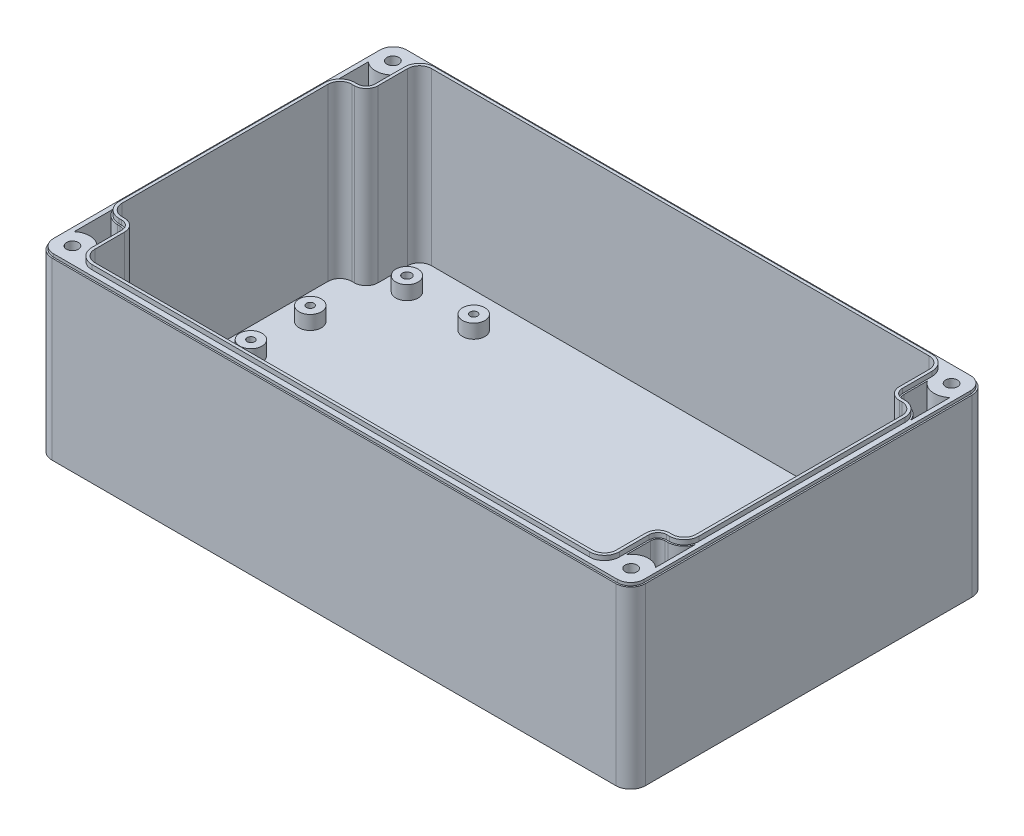
SolidWorks part; units mm, degrees
ref_plane "Front Plane" through (0, 0, 0) normal (0, 0, 1) x (1, 0, 0)
ref_plane "Top Plane" through (0, 0, 0) normal (0, 1, 0) x (1, 0, 0)
ref_plane "Right Plane" through (0, 0, 0) normal (1, 0, 0) x (0, 0, -1)
sketch "Sketch1" plane through (0, 0, 0) normal (0, 1, 0) x (1, 0, 0)
  line L1 (-100, 60) -> (100, 60)
  line L2 (-100, 60) -> (-100, -60)
  line L3 (-100, -60) -> (100, -60)
  line L4 (100, 60) -> (100, -60)
  line L5 (-100, 60) -> (100, -60) construction
  line L6 (-100, -60) -> (100, 60) construction
  point P0 (0, 0)
  dimension "D1" = 200
  dimension "D2" = 120
extrude "Boss-Extrude1" add sketch "Sketch1" along normal blind 60
fillet "Fillet1" radius 5 4 edges at (-100, 30, -60) (100, 30, -60) (100, 30, 60) (-100, 30, 60)
sketch "Sketch2" plane through (0, 60, 0) normal (0, 1, 0) x (1, 0, 0)
  line L0 (0, 60) -> (0, -60) construction
  line L1 (96.7, 56.7) -> (-96.7, 56.7)
  line L2 (96.7, 56.7) -> (96.7, -56.7)
  line L3 (96.7, -56.7) -> (-96.7, -56.7)
  line L4 (-96.7, 56.7) -> (-96.7, -56.7)
  line L5 (96.7, 56.7) -> (-96.7, -56.7) construction
  line L6 (96.7, -56.7) -> (-96.7, 56.7) construction
  line L7 (95, 60) -> (-95, 60) construction
  line L8 (-95, -60) -> (95, -60) construction
  line L9 (-100, 0) -> (99.9439, 0) construction
  line L10 (-100, 55) -> (-100, -55) construction
  line L12 (87.85, -56.7) -> (-87.85, -56.7)
  line L13 (87.85, -56.7) -> (87.85, 56.7)
  line L14 (87.85, 56.7) -> (-87.85, 56.7)
  line L15 (-87.85, -56.7) -> (-87.85, 56.7)
  line L16 (87.85, -56.7) -> (-87.85, 56.7) construction
  line L17 (87.85, 56.7) -> (-87.85, -56.7) construction
  line L18 (96.7, -38.7) -> (-96.7, -38.7)
  line L19 (96.7, -38.7) -> (96.7, 38.7)
  line L20 (96.7, 38.7) -> (-96.7, 38.7)
  line L21 (-96.7, -38.7) -> (-96.7, 38.7)
  line L22 (96.7, -38.7) -> (-96.7, 38.7) construction
  line L23 (96.7, 38.7) -> (-96.7, -38.7) construction
  circle A0 centre (-94.15, 54) radius 2
  circle A2 centre (94.15, 54) radius 2
  circle A3 centre (94.15, -54) radius 2
  circle A4 centre (-94.15, -54) radius 2
  point P0 (0, 0)
  point P18 (0, 0)
  point P19 (0, 0)
  dimension "D5" = 4
  dimension "D1" = 193.4
  dimension "D2" = 113.4
  dimension "D3" = 188.3
  dimension "D4" = 108
  dimension "D6" = 175.7
  dimension "D7" = 77.4
extrude "Cut-Extrude1" cut sketch "Sketch2" against normal offset from surface (56 mm away) 4 contours L20 L13 L1 L15 | L13 L20 L15 L18 | L13 L18 L15 L3 | L15 L20 L4 L18 | L2 L20 L13 L18 | A0 | A4 | A2 | A3 region at (0, 60, -47.7) region at (92.275, 60, 0) region at (0, 60, 0) region at (-92.275, 60, 0) region at (0, 60, 47.7) up to face at (0, 0, 0)
fillet "Fillet2" radius 4 12 edges at (87.85, 32, -56.7) (87.85, 32, -38.7) (96.7, 32, -38.7) (96.7, 32, 38.7) (87.85, 32, 38.7) (87.85, 32, 56.7) (-87.85, 32, 56.7) (-87.85, 32, 38.7) (-96.7, 32, 38.7) (-96.7, 32, -38.7) (-87.85, 32, -56.7) (-87.85, 32, -38.7)
sketch "Sketch3" plane through (0, 60, 0) normal (0, 1, 0) x (1, 0, 0)
  line L1 (83.85, 57.7) -> (-83.85, 57.7)
  line L2 (-88.85, 52.7) -> (-88.85, 42.7)
  line L3 (-91.85, 39.7) -> (-92.7, 39.7)
  line L4 (-97.7, 34.7) -> (-97.7, -34.7)
  line L5 (-92.7, -39.7) -> (-91.85, -39.7)
  line L6 (-88.85, -42.7) -> (-88.85, -52.7)
  line L7 (-83.85, -57.7) -> (83.85, -57.7)
  line L8 (88.85, -52.7) -> (88.85, -42.7)
  line L9 (91.85, -39.7) -> (92.7, -39.7)
  line L10 (97.7, -34.7) -> (97.7, 34.7)
  line L11 (92.7, 39.7) -> (91.85, 39.7)
  line L12 (88.85, 42.7) -> (88.85, 52.7)
  line L13 (87.85, 42.7) -> (87.85, 52.7)
  line L14 (92.7, 38.7) -> (91.85, 38.7)
  line L15 (96.7, -34.7) -> (96.7, 34.7)
  line L16 (91.85, -38.7) -> (92.7, -38.7)
  line L17 (87.85, -52.7) -> (87.85, -42.7)
  line L18 (-83.85, -56.7) -> (83.85, -56.7)
  line L19 (-87.85, -42.7) -> (-87.85, -52.7)
  line L20 (-92.7, -38.7) -> (-91.85, -38.7)
  line L21 (-96.7, 34.7) -> (-96.7, -34.7)
  line L22 (-91.85, 38.7) -> (-92.7, 38.7)
  line L23 (-87.85, 52.7) -> (-87.85, 42.7)
  line L24 (83.85, 56.7) -> (-83.85, 56.7)
  line L25 (87.85, 42.7) -> (87.85, 52.7)
  line L26 (92.7, 38.7) -> (91.85, 38.7)
  line L27 (96.7, -34.7) -> (96.7, 34.7)
  line L28 (91.85, -38.7) -> (92.7, -38.7)
  line L29 (87.85, -52.7) -> (87.85, -42.7)
  line L30 (-83.85, -56.7) -> (83.85, -56.7)
  line L31 (-87.85, -42.7) -> (-87.85, -52.7)
  line L32 (-92.7, -38.7) -> (-91.85, -38.7)
  line L33 (-96.7, 34.7) -> (-96.7, -34.7)
  line L34 (-91.85, 38.7) -> (-92.7, 38.7)
  line L35 (-87.85, 52.7) -> (-87.85, 42.7)
  line L36 (83.85, 56.7) -> (-83.85, 56.7)
  arc A0 (-83.85, 57.7) -> (-88.85, 52.7) centre (-83.85, 52.7) ccw
  arc A1 (-91.85, 39.7) -> (-88.85, 42.7) centre (-91.85, 42.7) ccw
  arc A2 (-92.7, 39.7) -> (-97.7, 34.7) centre (-92.7, 34.7) ccw
  arc A3 (-97.7, -34.7) -> (-92.7, -39.7) centre (-92.7, -34.7) ccw
  arc A4 (-88.85, -42.7) -> (-91.85, -39.7) centre (-91.85, -42.7) ccw
  arc A5 (-88.85, -52.7) -> (-83.85, -57.7) centre (-83.85, -52.7) ccw
  arc A6 (83.85, -57.7) -> (88.85, -52.7) centre (83.85, -52.7) ccw
  arc A7 (91.85, -39.7) -> (88.85, -42.7) centre (91.85, -42.7) ccw
  arc A8 (92.7, -39.7) -> (97.7, -34.7) centre (92.7, -34.7) ccw
  arc A9 (97.7, 34.7) -> (92.7, 39.7) centre (92.7, 34.7) ccw
  arc A10 (88.85, 42.7) -> (91.85, 39.7) centre (91.85, 42.7) ccw
  arc A11 (88.85, 52.7) -> (83.85, 57.7) centre (83.85, 52.7) ccw
  arc A12 (87.85, 42.7) -> (91.85, 38.7) centre (91.85, 42.7) ccw
  arc A13 (96.7, 34.7) -> (92.7, 38.7) centre (92.7, 34.7) ccw
  arc A14 (92.7, -38.7) -> (96.7, -34.7) centre (92.7, -34.7) ccw
  arc A15 (91.85, -38.7) -> (87.85, -42.7) centre (91.85, -42.7) ccw
  arc A16 (83.85, -56.7) -> (87.85, -52.7) centre (83.85, -52.7) ccw
  arc A17 (-87.85, -52.7) -> (-83.85, -56.7) centre (-83.85, -52.7) ccw
  arc A18 (-87.85, -42.7) -> (-91.85, -38.7) centre (-91.85, -42.7) ccw
  arc A19 (-96.7, -34.7) -> (-92.7, -38.7) centre (-92.7, -34.7) ccw
  arc A20 (-92.7, 38.7) -> (-96.7, 34.7) centre (-92.7, 34.7) ccw
  arc A21 (-91.85, 38.7) -> (-87.85, 42.7) centre (-91.85, 42.7) ccw
  arc A22 (-83.85, 56.7) -> (-87.85, 52.7) centre (-83.85, 52.7) ccw
  arc A23 (87.85, 52.7) -> (83.85, 56.7) centre (83.85, 52.7) ccw
  arc A24 (87.85, 42.7) -> (91.85, 38.7) centre (91.85, 42.7) ccw
  arc A25 (96.7, 34.7) -> (92.7, 38.7) centre (92.7, 34.7) ccw
  arc A26 (92.7, -38.7) -> (96.7, -34.7) centre (92.7, -34.7) ccw
  arc A27 (91.85, -38.7) -> (87.85, -42.7) centre (91.85, -42.7) ccw
  arc A28 (83.85, -56.7) -> (87.85, -52.7) centre (83.85, -52.7) ccw
  arc A29 (-87.85, -52.7) -> (-83.85, -56.7) centre (-83.85, -52.7) ccw
  arc A30 (-87.85, -42.7) -> (-91.85, -38.7) centre (-91.85, -42.7) ccw
  arc A31 (-96.7, -34.7) -> (-92.7, -38.7) centre (-92.7, -34.7) ccw
  arc A32 (-92.7, 38.7) -> (-96.7, 34.7) centre (-92.7, 34.7) ccw
  arc A33 (-91.85, 38.7) -> (-87.85, 42.7) centre (-91.85, 42.7) ccw
  arc A34 (-83.85, 56.7) -> (-87.85, 52.7) centre (-83.85, 52.7) ccw
  arc A35 (87.85, 52.7) -> (83.85, 56.7) centre (83.85, 52.7) ccw
  dimension "D1" = 0
  dimension "D2" = 1
extrude "Boss-Extrude2" add sketch "Sketch3" along normal blind 1.55
sketch "Sketch4" plane through (0, 4, 0) normal (0, 1, 0) x (1, 0, 0)
  circle A1 centre (-94.15, 54) radius 2
  circle A2 centre (-94.15, 54) radius 2
  circle A3 centre (94.15, 54) radius 2
  circle A4 centre (94.15, 54) radius 2
  circle A5 centre (-94.15, -54) radius 2
  circle A6 centre (-94.15, -54) radius 2
  circle A7 centre (94.15, -54) radius 2
  circle A8 centre (94.15, -54) radius 2
  dimension "D1" = 0
  dimension "D2" = 0
  dimension "D3" = 0
  dimension "D4" = 0
extrude "Cut-Extrude2" cut sketch "Sketch4" against normal up to next
sketch "Sketch5" plane through (0, 0, 0) normal (0, -1, 0) x (1, 0, 0)
  circle A0 centre (-94.15, 54) radius 3.45
  circle A1 centre (94.15, 54) radius 3.45
  circle A2 centre (94.15, -54) radius 3.45
  circle A3 centre (-94.15, -54) radius 3.45
  dimension "D1" = 6.9
extrude "Cut-Extrude3" cut sketch "Sketch5" against normal blind 52
sketch "Sketch6" plane through (0, 60, 0) normal (0, 1, 0) x (1, 0, 0)
  line L8 (95, 58) -> (-95, 58)
  line L9 (-98, 55) -> (-98, -55)
  line L10 (-95, -58) -> (95, -58)
  line L11 (98, -55) -> (98, 55)
  line L12 (95, 58) -> (-95, 58)
  line L13 (-98, 55) -> (-98, -55)
  line L14 (-95, -58) -> (95, -58)
  line L15 (98, -55) -> (98, 55)
  line L25 (-100, 55) -> (-100, -55) construction
  line L37 (83.85, 58.2) -> (-83.85, 58.2)
  line L38 (89.35, 42.7) -> (89.35, 52.7)
  line L39 (92.7, 40.2) -> (91.85, 40.2)
  line L40 (98.2, -34.7) -> (98.2, 34.7)
  line L41 (91.85, -40.2) -> (92.7, -40.2)
  line L42 (89.35, -52.7) -> (89.35, -42.7)
  line L43 (-83.85, -58.2) -> (83.85, -58.2)
  line L44 (-89.35, -42.7) -> (-89.35, -52.7)
  line L45 (-92.7, -40.2) -> (-91.85, -40.2)
  line L46 (-98.2, 34.7) -> (-98.2, -34.7)
  line L47 (-91.85, 40.2) -> (-92.7, 40.2)
  line L48 (-89.35, 52.7) -> (-89.35, 42.7)
  line L49 (83.85, 58.2) -> (-83.85, 58.2)
  line L50 (89.35, 42.7) -> (89.35, 52.7)
  line L51 (92.7, 40.2) -> (91.85, 40.2)
  line L52 (98.2, -34.7) -> (98.2, 34.7)
  line L53 (91.85, -40.2) -> (92.7, -40.2)
  line L54 (89.35, -52.7) -> (89.35, -42.7)
  line L55 (-83.85, -58.2) -> (83.85, -58.2)
  line L56 (-89.35, -42.7) -> (-89.35, -52.7)
  line L57 (-92.7, -40.2) -> (-91.85, -40.2)
  line L58 (-98.2, 34.7) -> (-98.2, -34.7)
  line L59 (-91.85, 40.2) -> (-92.7, 40.2)
  line L60 (-89.35, 52.7) -> (-89.35, 42.7)
  arc A8 (-95, 58) -> (-98, 55) centre (-95, 55) ccw
  arc A9 (-98, -55) -> (-95, -58) centre (-95, -55) ccw
  arc A10 (95, -58) -> (98, -55) centre (95, -55) ccw
  arc A11 (98, 55) -> (95, 58) centre (95, 55) ccw
  arc A12 (-95, 58) -> (-98, 55) centre (-95, 55) ccw
  arc A13 (-98, -55) -> (-95, -58) centre (-95, -55) ccw
  arc A14 (95, -58) -> (98, -55) centre (95, -55) ccw
  arc A15 (98, 55) -> (95, 58) centre (95, 55) ccw
  circle A24 centre (-94.15, 54) radius 5.85
  circle A25 centre (94.15, 54) radius 5.85
  circle A26 centre (94.15, -54) radius 5.85
  circle A27 centre (-94.15, -54) radius 5.85
  arc A36 (89.35, 52.7) -> (83.85, 58.2) centre (83.85, 52.7) ccw
  arc A37 (89.35, 42.7) -> (91.85, 40.2) centre (91.85, 42.7) ccw
  arc A38 (98.2, 34.7) -> (92.7, 40.2) centre (92.7, 34.7) ccw
  arc A39 (92.7, -40.2) -> (98.2, -34.7) centre (92.7, -34.7) ccw
  arc A40 (91.85, -40.2) -> (89.35, -42.7) centre (91.85, -42.7) ccw
  arc A41 (83.85, -58.2) -> (89.35, -52.7) centre (83.85, -52.7) ccw
  arc A42 (-89.35, -52.7) -> (-83.85, -58.2) centre (-83.85, -52.7) ccw
  arc A43 (-89.35, -42.7) -> (-91.85, -40.2) centre (-91.85, -42.7) ccw
  arc A44 (-98.2, -34.7) -> (-92.7, -40.2) centre (-92.7, -34.7) ccw
  arc A45 (-92.7, 40.2) -> (-98.2, 34.7) centre (-92.7, 34.7) ccw
  arc A46 (-91.85, 40.2) -> (-89.35, 42.7) centre (-91.85, 42.7) ccw
  arc A47 (-83.85, 58.2) -> (-89.35, 52.7) centre (-83.85, 52.7) ccw
  arc A48 (89.35, 52.7) -> (83.85, 58.2) centre (83.85, 52.7) ccw
  arc A49 (89.35, 42.7) -> (91.85, 40.2) centre (91.85, 42.7) ccw
  arc A50 (98.2, 34.7) -> (92.7, 40.2) centre (92.7, 34.7) ccw
  arc A51 (92.7, -40.2) -> (98.2, -34.7) centre (92.7, -34.7) ccw
  arc A52 (91.85, -40.2) -> (89.35, -42.7) centre (91.85, -42.7) ccw
  arc A53 (83.85, -58.2) -> (89.35, -52.7) centre (83.85, -52.7) ccw
  arc A54 (-89.35, -52.7) -> (-83.85, -58.2) centre (-83.85, -52.7) ccw
  arc A55 (-89.35, -42.7) -> (-91.85, -40.2) centre (-91.85, -42.7) ccw
  arc A56 (-98.2, -34.7) -> (-92.7, -40.2) centre (-92.7, -34.7) ccw
  arc A57 (-92.7, 40.2) -> (-98.2, 34.7) centre (-92.7, 34.7) ccw
  arc A58 (-91.85, 40.2) -> (-89.35, 42.7) centre (-91.85, 42.7) ccw
  arc A59 (-83.85, 58.2) -> (-89.35, 52.7) centre (-83.85, 52.7) ccw
  dimension "D1" = 2
  dimension "D2" = 0.5
extrude "Cut-Extrude4" cut sketch "Sketch6" against normal up to surface (56 mm away) contours L59 A58 L60 A24 L13 A57 | A50 L15 A25 L50 A49 L51 | L53 A52 L54 A26 L15 A51 | A56 L13 A27 L56 A55 L57 region at (93.8916, 60, -44.1874) region at (93.8916, 60, 44.1874) region at (-93.8916, 60, -44.1874) region at (-93.8916, 60, 44.1874) up to face at (0, 4, 0)
sketch "Sketch7" plane through (0, 0, 0) normal (0, -1, 0) x (1, 0, 0)
  line L0 (-94.15, 54) -> (-94.15, -54) construction
  line L1 (94.15, -45) -> (-94.15, -45)
  line L2 (94.15, -45) -> (94.15, 45)
  line L3 (94.15, 45) -> (-94.15, 45)
  line L4 (-94.15, -45) -> (-94.15, 45)
  line L5 (94.15, -45) -> (-94.15, 45) construction
  line L6 (94.15, 45) -> (-94.15, -45) construction
  circle A0 centre (-94.15, 45) radius 2.225
  circle A1 centre (94.15, 45) radius 2.225
  circle A2 centre (94.15, -45) radius 2.225
  circle A3 centre (-94.15, -45) radius 2.225
  point P0 (0, 0)
  dimension "D2" = 4.45
  dimension "D1" = 90
extrude "Cut-Extrude5" cut sketch "Sketch7" against normal up to next contours A0 | A1 | A2 | A3
sketch "Sketch8" plane through (0, 4, 0) normal (0, 1, 0) x (1, 0, 0)
  line L0 (0, 60) -> (0, -60) construction
  line L1 (95, 60) -> (-95, 60) construction
  line L2 (-95, -60) -> (95, -60) construction
  line L3 (-100, 0) -> (100, 0) construction
  line L4 (-100, 55) -> (-100, -55) construction
  line L5 (100, -55) -> (100, 55) construction
  line L6 (-80.4, 45) -> (80.4, 45) construction
  line L7 (-80.4, 45) -> (-80.4, -45) construction
  line L8 (-88, 60) -> (-88, -60) construction
  circle A0 centre (-80.4, 45) radius 3.75
  circle A1 centre (-80.4, 45) radius 1.5
  circle A2 centre (80.4, 45) radius 3.75
  circle A3 centre (80.4, 45) radius 1.5
  circle A4 centre (80.4, -45) radius 3.75
  circle A5 centre (80.4, -45) radius 1.5
  circle A6 centre (-80.4, -45) radius 3.75
  circle A7 centre (-80.4, -45) radius 1.5
  circle A8 centre (-57.9, 45) radius 3.75
  circle A9 centre (-57.9, 45) radius 1.25
  circle A12 centre (-57.9, -45) radius 1.25
  circle A13 centre (-57.9, -45) radius 3.75
  circle A16 centre (-88, 0) radius 3.75
  circle A17 centre (-88, 0) radius 1.25
  circle A18 centre (-88, 20) radius 3.75
  circle A19 centre (-88, 20) radius 1.25
  circle A20 centre (-88, -20) radius 1.25
  circle A21 centre (-88, -20) radius 3.75
  circle A22 centre (88, -20) radius 3.75
  circle A23 centre (88, -20) radius 1.25
  circle A24 centre (88, 0) radius 1.25
  circle A25 centre (88, 0) radius 3.75
  circle A26 centre (88, 20) radius 3.75
  circle A27 centre (88, 20) radius 1.25
  dimension "D1" = 7.5
  dimension "D2" = 3
  dimension "D5" = 2.5
  dimension "D3" = 160.8
  dimension "D4" = 90
  dimension "D6" = 22.5
  dimension "D7" = 176
  dimension "D8" = 40
extrude "Boss-Extrude3" add sketch "Sketch8" along normal blind 4.7
sketch "Sketch9" plane through (0, 60, 0) normal (0, 1, 0) x (1, 0, 0)
  line L0 (95, 59.5) -> (-95, 59.5)
  line L1 (-99.5, 55) -> (-99.5, -55)
  line L2 (-95, -59.5) -> (95, -59.5)
  line L3 (99.5, -55) -> (99.5, 55)
  line L4 (95, 60) -> (-95, 60)
  line L5 (-100, 55) -> (-100, -55)
  line L6 (-95, -60) -> (95, -60)
  line L7 (100, -55) -> (100, 55)
  line L8 (95, 60) -> (-95, 60)
  line L9 (-100, 55) -> (-100, -55)
  line L10 (-95, -60) -> (95, -60)
  line L11 (100, -55) -> (100, 55)
  arc A0 (-95, 59.5) -> (-99.5, 55) centre (-95, 55) ccw
  arc A1 (-99.5, -55) -> (-95, -59.5) centre (-95, -55) ccw
  arc A2 (95, -59.5) -> (99.5, -55) centre (95, -55) ccw
  arc A3 (99.5, 55) -> (95, 59.5) centre (95, 55) ccw
  arc A4 (-95, 60) -> (-100, 55) centre (-95, 55) ccw
  arc A5 (-100, -55) -> (-95, -60) centre (-95, -55) ccw
  arc A6 (95, -60) -> (100, -55) centre (95, -55) ccw
  arc A7 (100, 55) -> (95, 60) centre (95, 55) ccw
  arc A8 (-95, 60) -> (-100, 55) centre (-95, 55) ccw
  arc A9 (-100, -55) -> (-95, -60) centre (-95, -55) ccw
  arc A10 (95, -60) -> (100, -55) centre (95, -55) ccw
  arc A11 (100, 55) -> (95, 60) centre (95, 55) ccw
  dimension "D1" = 0
  dimension "D2" = 0.5
extrude "Cut-Extrude6" cut sketch "Sketch9" against normal blind 1
sketch "Sketch10" [suppressed] plane through (0, 8.7, 0) normal (0, 1, 0) x (1, 0, 0)
  circle A1 centre (-57.9, 45) radius 3.75
  circle A2 centre (-57.9, 45) radius 3.75
  dimension "D1" = 0
extrude "Cut-Extrude7" [suppressed] cut sketch "Sketch10" against normal up to surface (4.7 mm away) up to face at (88, 4, -23.75)
